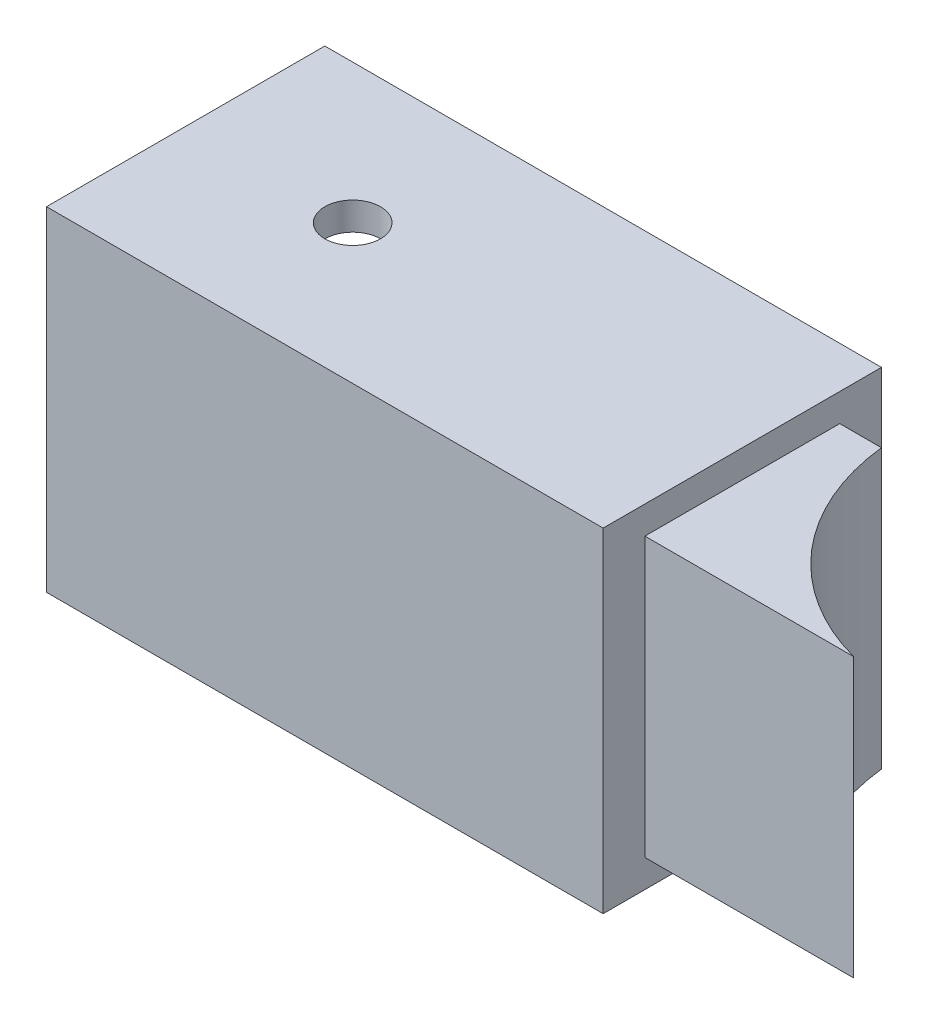
SolidWorks part; units mm, degrees
ref_plane "Front Plane" through (0, 0, 0) normal (0, 0, 1) x (1, 0, 0)
ref_plane "Top Plane" through (0, 0, 0) normal (0, 1, 0) x (1, 0, 0)
ref_plane "Right Plane" through (0, 0, 0) normal (1, 0, 0) x (0, 0, -1)
sketch "Sketch2" plane through (0, 0, 0) normal (0, 0, 1) x (1, 0, 0)
  line L1 (-50, -30) -> (50, -30)
  line L2 (-50, -30) -> (-50, 30)
  line L3 (-50, 30) -> (50, 30)
  line L4 (50, -30) -> (50, 30)
  line L5 (-50, -30) -> (50, 30) construction
  line L6 (-50, 30) -> (50, -30) construction
  point P0 (0, 0)
  dimension "D1" = 100
  dimension "D2" = 60
extrude "Boss-Extrude1" add sketch "Sketch2" along normal blind 50 contours L3 L4 L1 L2
shell "Shell1" thickness 5 removed face at (-50, 0, 25)
sketch "Sketch4" plane through (0, 0, 5) normal (0, 0, 1) x (1, 0, 0)
  line L0 (-50, -25) -> (45, -25) construction
  line L5 (-50, 25) -> (10, 25)
  line L6 (-50, 25) -> (-50, -25)
  line L7 (-50, -25) -> (10, -25)
  line L8 (10, 25) -> (10, -25)
  dimension "D1" = 60
extrude "Cut-Extrude1" cut sketch "Sketch4" against normal blind 10
sketch "Sketch5" plane through (0, -25, 0) normal (0, 1, 0) x (1, 0, 0)
  line L0 (-50, -50) -> (-50, 0) construction
  circle A1 centre (-20, -25) radius 5
  dimension "D3" = 10
  dimension "D1" = 30
extrude "Cut-Extrude2" cut sketch "Sketch5" against normal through all both and the other way through all
sketch "Sketch13" plane through (0, 30, 0) normal (0, 1, 0) x (1, 0, 0)
  line L5 (-50, 0) -> (50, 0) construction
  line L6 (57.5, -42.5) -> (87.5, -42.5)
  line L8 (50, -50) -> (50, 0) construction
  line L9 (50, -7.5) -> (57.5, -7.5)
  line L10 (50, -7.5) -> (50, -42.5)
  line L11 (50, -42.5) -> (57.5, -42.5)
  arc A1 (87.5, -42.5) -> (57.5, -7.5) centre (98.1389, -3.0238) cw
  dimension "D1" = 30
  dimension "D2" = 7.5
  dimension "D3" = 7.5
extrude "Boss-Extrude2" add sketch "Sketch13" against normal blind 60 contours L10 L11 L6 A1 L9
ref_plane "Plane2" through (87.5, 0, 0) normal (1, 0, 0) x (0, 1, 0)
sketch "Sketch15" plane through (87.5, 0, 0) normal (1, 0, 0) x (0, 1, 0)
  line L0 (-30, 0) -> (30, 0) construction
  line L1 (-30, 50) -> (-25, 50)
  line L2 (-30, 50) -> (-30, 0)
  line L3 (-30, 0) -> (-25, 0)
  line L4 (-25, 50) -> (-25, 0)
  line L6 (30, 50) -> (25, 50)
  line L7 (30, 50) -> (30, 0)
  line L8 (30, 0) -> (25, 0)
  line L9 (25, 50) -> (25, 0)
  dimension "D1" = 5
  dimension "D2" = 5
extrude "Cut-Extrude4" cut sketch "Sketch15" against normal up to surface (37.5 mm away) up to face at (50, 0, 46.25)
shell "Shell3" thickness 5 removed face at (45, 0, 25)
